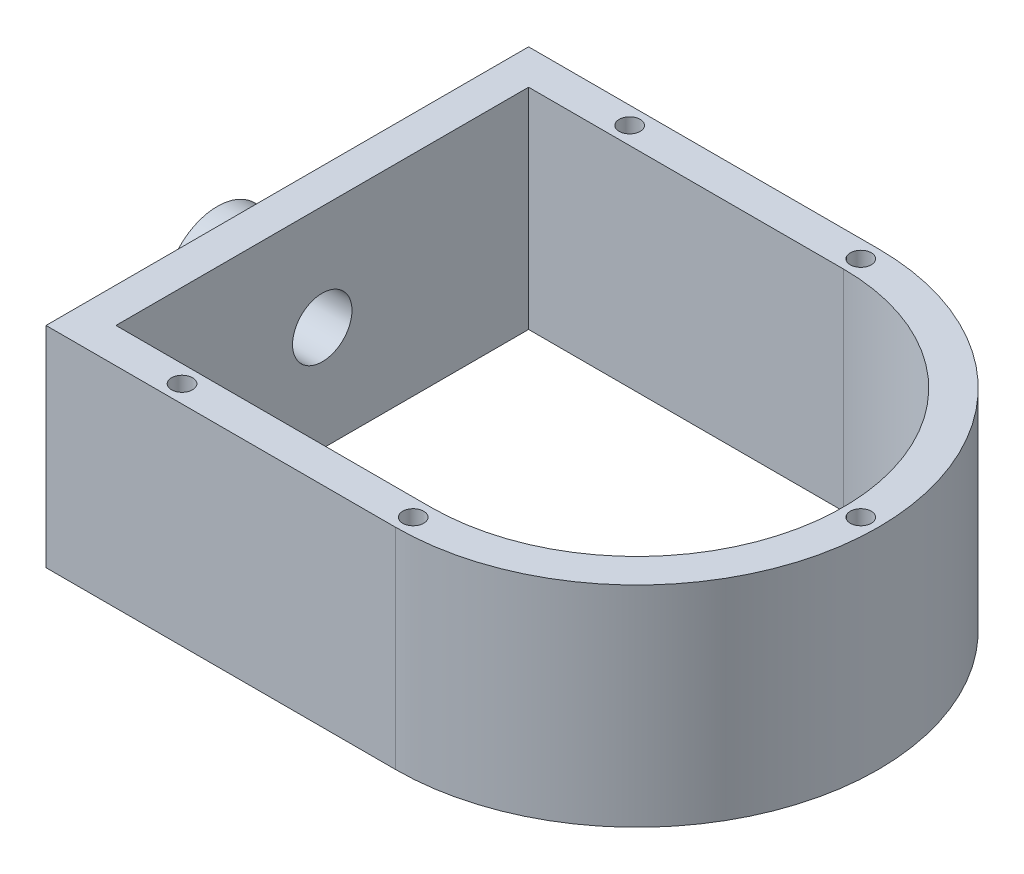
SolidWorks part; units mm, degrees
ref_plane "Front Plane" through (0, 0, 0) normal (0, 0, 1) x (1, 0, 0)
ref_plane "Top Plane" through (0, 0, 0) normal (0, 1, 0) x (1, 0, 0)
ref_plane "Right Plane" through (0, 0, 0) normal (1, 0, 0) x (0, 0, -1)
sketch "Sketch1" plane through (0, 0, 0) normal (0, 1, 0) x (1, 0, 0)
  line L5 (10, -34.5) -> (-40, -34.5)
  line L6 (-40, -34.5) -> (-40, 34.5)
  line L11 (-40, 34.5) -> (10, 34.5)
  line L13 (30, 21.6852) -> (30, -21.6852)
  line L15 (-35, 29.5) -> (10, 29.5)
  line L16 (10, -29.5) -> (-35, -29.5)
  line L17 (-35, -29.5) -> (-35, 29.5)
  line L18 (30, 18.02) -> (30, -9.5987)
  arc A5 (10, 29.5) -> (10, -29.5) centre (10, 0) cw
  arc A6 (30, 21.6852) -> (30, -21.6852) centre (10, 0) cw
  arc A8 (10, 34.5) -> (10, -34.5) centre (10, 0) cw
  arc A9 (10, 34.5) -> (10, -34.5) centre (10, 0) cw construction
  circle A10 centre (35, 0) radius 2.5
  circle A11 centre (-23.05, 32) radius 1.5
  circle A12 centre (-23.05, -32) radius 1.5
  circle A13 centre (10, 32) radius 1.5
  circle A14 centre (10, -32) radius 1.5
  circle A15 centre (42, 0) radius 1.5
  point P0 (0, 0)
  point P23 (0, 0)
  point P30 (39.5, 0)
  dimension "D4" = 5
  dimension "D9" = 3
  dimension "D10" = 3
  dimension "D13" = 3
  dimension "D14" = 3
  dimension "D15" = 3
  dimension "D6" = 45
  dimension "D1" = 34.5
  dimension "D2" = 69
  dimension "D5" = 25
  dimension "D7" = 10
  dimension "D8" = 5
  dimension "D11" = 2.5
  dimension "D12" = 2.5
  dimension "D16" = 2.5
  dimension "D17" = 2.5
  dimension "D18" = 2.5
  dimension "D3" = 5
extrude "Boss-Extrude1" add sketch "Sketch1" along normal blind 30 contours A8 L11 L6 L5 L15 A5 L16 L17 region at (-15, 0, 33.4091)
extrude "Boss-Extrude2" add sketch "Sketch1<4>" along normal blind 3 contours A5 L13 A10 region at (39.056, 0, 0)
sketch "Sketch1<4>" plane through (0, 0, 0) normal (0, 1, 0) x (1, 0, 0) same geometry as "Sketch1"
sketch "Sketch2" plane through (-40, 0, 0) normal (-1, 0, 0) x (0, 0, 1)
  line L0 (-34.5, 30) -> (34.5, 0) construction
  circle A0 centre (0, 15) radius 4.25
  dimension "D1" = 8.5
extrude "Cut-Extrude1" cut sketch "Sketch2" against normal blind 3
sketch "Sketch3" plane through (-40, 0, 0) normal (-1, 0, 0) x (0, 0, 1)
  circle A0 centre (0, 15) radius 4.25 construction
  circle A1 centre (0, 15) radius 4.25
  circle A2 centre (0, 15) radius 7.5
  dimension "D1" = 15
extrude "Boss-Extrude3" add sketch "Sketch3" along normal blind 10
fillet "Fillet1" radius 5 1 edges at (-40, 15, 7.5)
sketch "Sketch4" plane through (-37, 0, 0) normal (-1, 0, 0) x (0, 0, 1)
  circle A1 centre (0, 15) radius 4.25
  circle A2 centre (0, 15) radius 4.25
  dimension "D1" = 0
extrude "Cut-Extrude2" cut sketch "Sketch4" against normal blind 10
equation "\"D1@Sketch1\"=\"D2@Sketch1\"/2"
equation "\"D11@Sketch1\"=\"D3@Sketch1\"/2"
equation "\"D12@Sketch1\"=\"D11@Sketch1\""
equation "\"D16@Sketch1\"=\"D12@Sketch1\""
equation "\"D17@Sketch1\"=\"D12@Sketch1\""
equation "\"D18@Sketch1\"=\"D12@Sketch1\""
